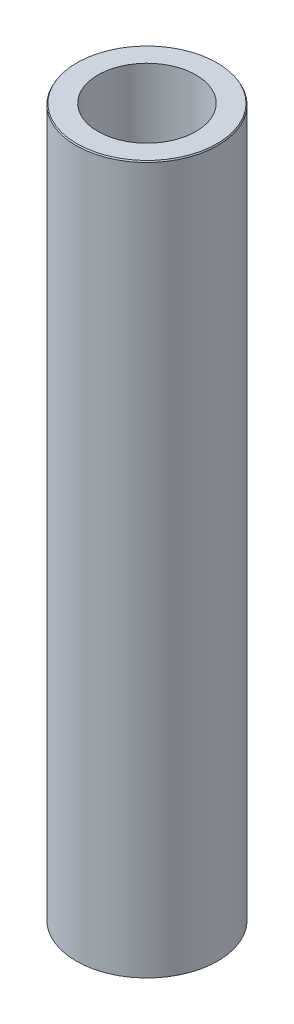
SolidWorks part; units mm, degrees
ref_plane "Front Plane" through (0, 0, 0) normal (0, 0, 1) x (1, 0, 0)
ref_plane "Top Plane" through (0, 0, 0) normal (0, 1, 0) x (1, 0, 0)
ref_plane "Right Plane" through (0, 0, 0) normal (1, 0, 0) x (0, 0, -1)
sketch "Sketch1" plane through (0, 0, 0) normal (0, 1, 0) x (1, 0, 0)
  circle A0 centre (0, 0) radius 60
  dimension "SHAFT_OD" = 120
extrude "Boss-Extrude1" add sketch "Sketch1" along normal blind 600
sketch "Sketch2" plane through (0, 0, 0) normal (0, 1, 0) x (1, 0, 0)
  circle A0 centre (0, 0) radius 41.5115
  dimension "BORE_D" = 83.023
extrude "Cut-Extrude1" cut sketch "Sketch2" along normal through all
chamfer "Chamfer1" distance 1.0902 angle 30 2 edges at (0, 600, 60) (0, 0, 60) first distance on face at (0, 600, 60) first distance on face at (0, 0, 41.5115)
